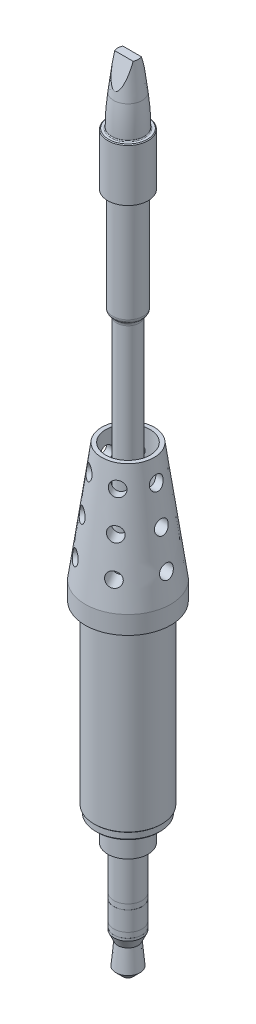
SolidWorks part; units mm, degrees
other "Body"
other "Jack Base"
other "Jack Divider 1"
other "Jack Middle"
other "Jack Divider 2"
other "Jack Tip"
other "Guard"
ref_plane "Front Plane" through (0, 0, 0) normal (0, 0, 1) x (1, 0, 0)
ref_plane "Top Plane" through (0, 0, 0) normal (0, 1, 0) x (1, 0, 0)
ref_plane "Right Plane" through (0, 0, 0) normal (1, 0, 0) x (0, 0, -1)
sketch "Sketch1" plane through (0, 0, 0) normal (0, 1, 0) x (1, 0, 0)
  circle A0 centre (0, 0) radius 4.2
  dimension "D1" = 8.4
extrude "Boss-Extrude1" add sketch "Sketch1" along normal blind 22
sketch "Sketch9" plane through (0, 22, 0) normal (0, 1, 0) x (1, 0, 0)
  circle A0 centre (0, 0) radius 3.4
  dimension "D1" = 6.8
extrude "Boss-Extrude8" add sketch "Sketch9" along normal blind 0.7
sketch "Sketch10" plane through (0, 22.7, 0) normal (0, 1, 0) x (1, 0, 0)
  circle A0 centre (0, 0) radius 3.75
  dimension "D1" = 7.5
extrude "Boss-Extrude9" add sketch "Sketch10" along normal blind 2.8
sketch "Sketch11" plane through (0, 25.5, 0) normal (0, 1, 0) x (1, 0, 0)
  circle A0 centre (0, 0) radius 1.8
  dimension "D1" = 3.6
extrude "Boss-Extrude10" add sketch "Sketch11" along normal blind 2.9
sketch "Sketch12" plane through (0, 28.4, 0) normal (0, 1, 0) x (1, 0, 0)
  circle A0 centre (0, 0) radius 1.4
  dimension "D1" = 2.8
extrude "Boss-Extrude11" add sketch "Sketch12" along normal blind 24.25
sketch "Sketch13" plane through (0, 52.65, 0) normal (0, 1, 0) x (1, 0, 0)
  circle A0 centre (0, 0) radius 1.9
  dimension "D1" = 3.8
extrude "Boss-Extrude12" add sketch "Sketch13" along normal blind 13.2
sketch "Sketch14" plane through (0, 65.85, 0) normal (0, 1, 0) x (1, 0, 0)
  circle A0 centre (0, 0) radius 2.5
  dimension "D1" = 5
extrude "Boss-Extrude13" add sketch "Sketch14" along normal blind 6.9
sketch "Sketch15" plane through (0, 0, 0) normal (1, 0, 0) x (0, 0, -1)
  line L0 (0, -927.2764) -> (0, 49072.7236) construction
  line L2 (-2, 72.75) -> (-2, 74.75)
  line L3 (2.5, 72.75) -> (-2.5, 72.75) construction
  line L4 (-2, 74.75) -> (-1.25, 80.75)
  line L5 (-1.25, 80.75) -> (0, 80.75)
  line L6 (0, 80.75) -> (0, 72.75)
  line L7 (0, 72.75) -> (-2, 72.75)
  dimension "D1" = 4
  dimension "D2" = 2.5
  dimension "D3" = 8
  dimension "D4" = 2
revolve "Revolve2" add sketch "Sketch15" angle 360 about L0
sketch "Sketch16" plane through (0, 0, 0) normal (1, 0, 0) x (0, 0, -1)
  line L0 (1.25, 80.75) -> (-1.25, 80.75) construction
  line L1 (2, 74.75) -> (-2, 74.75) construction
  line L3 (1.25, 80.75) -> (-1.25, 80.75) construction
  line L4 (-1.25, 80.75) -> (-2.1233, 74.75) construction
  line L5 (1.25, 80.75) -> (2, 74.75) construction
  line L6 (-0.5, 80.75) -> (0.5, 80.75)
  line L7 (0.5, 80.75) -> (1.65, 77.5504)
  line L8 (1.65, 77.5504) -> (1.25, 80.75)
  line L9 (1.25, 80.75) -> (0.5, 80.75)
  line L10 (0, 4.62) -> (0, -4.62) construction
  line L11 (-1.65, 77.5504) -> (-1.25, 80.75)
  line L12 (-0.5, 80.75) -> (-1.65, 77.5504)
  line L13 (-1.25, 80.75) -> (-0.5, 80.75)
  point P7 (0, 80.75)
  dimension "D2" = 1
  dimension "D3" = 3.4
extrude "Cut-Extrude1" cut sketch "Sketch16" against normal through all both and the other way through all contours L13 L11 L12 | L8 L9 L7 region at (0, 79.6835, -1.1333) region at (0, 79.6835, 1.1333)
fillet "Fillet1" radius 30 1 edges at (0, 74.75, -2)
chamfer "Chamfer1" distance 0.1 angle 45 2 edges at (0, 0, 4.2) (0, 72.75, 2.5)
chamfer "Chamfer2" distance 0.4 angle 45 2 edges at (0, 25.5, 3.75) (0, 22.7, 3.75)
chamfer "Chamfer3" distance 0.6 angle 30 1 edges at (0, 65.85, 2.5) first distance on face at (0, 65.85, 1.9)
fillet "Fillet3" radius 0.1 1 edges at (0, 72.75, -2)
chamfer "Chamfer4" distance 0.6 angle 45 1 edges at (0, 52.65, 1.9)
fillet "Fillet4" radius 0.6 2 edges at (0, 52.75, 1.4) (0, 53.25, 1.9)
sketch "Sketch2" plane through (0, 0, 0) normal (0, -1, 0) x (1, 0, 0)
  circle A0 centre (0, 0) radius 4
  dimension "D1" = 8
extrude "Boss-Extrude2" add sketch "Sketch2" along normal blind 1 separate body
sketch "Sketch3" plane through (0, -1, 0) normal (0, -1, 0) x (1, 0, 0)
  circle A0 centre (0, 0) radius 2.5
  dimension "D1" = 5
extrude "Boss-Extrude3" add sketch "Sketch3" along normal blind 3
sketch "Sketch4" plane through (0, -4, 0) normal (0, -1, 0) x (1, 0, 0)
  circle A0 centre (0, 0) radius 1.75
  dimension "D1" = 3.5
extrude "Boss-Extrude4" add sketch "Sketch4" along normal blind 5.35
sketch "Sketch5" plane through (0, -9.35, 0) normal (0, -1, 0) x (1, 0, 0)
  circle A2 centre (0, 0) radius 1.74
  circle A3 centre (0, 0) radius 1.74
  dimension "D1" = 0.01
extrude "Boss-Extrude5" add sketch "Sketch5" along normal blind 0.65 separate body
sketch "Sketch6" plane through (0, -10, 0) normal (0, -1, 0) x (1, 0, 0)
  circle A0 centre (0, 0) radius 1.75 construction
  circle A1 centre (0, 0) radius 1.75
extrude "Boss-Extrude6" add sketch "Sketch6" along normal blind 2.4 separate body
sketch "Sketch7" plane through (0, -12.4, 0) normal (0, -1, 0) x (1, 0, 0)
  circle A2 centre (0, 0) radius 1.74
  circle A3 centre (0, 0) radius 1.74
  dimension "D1" = 0.01
extrude "Boss-Extrude7" add sketch "Sketch7" along normal blind 0.65 separate body
sketch "Sketch8" plane through (0, 0, 0) normal (1, 0, 0) x (0, 0, -1)
  line L0 (0, -1013.0181) -> (0, 48986.9819) construction
  line L2 (0, -13.05) -> (-1.75, -13.05)
  line L3 (-1.74, -13.05) -> (1.74, -13.05) construction
  line L4 (-1.75, -13.05) -> (-1.75, -13.35)
  line L5 (-1.75, -13.35) -> (-1.25, -14.4362)
  line L6 (-1.25, -14.4362) -> (-1.5, -17.225)
  line L7 (-1.5, -17.225) -> (-0.625, -18.1)
  line L8 (-0.625, -18.1) -> (0, -18.1)
  line L9 (0, -18.1) -> (0, -13.05)
  line L10 (-4, -1) -> (4, -1) construction
  point P12 (-0.3125, -18.1)
  dimension "D1" = 3.5
  dimension "D2" = 3
  dimension "D3" = 1.25
  dimension "D4" = 17.1
  dimension "D5" = 2.5
  dimension "D6" = 0.3
  dimension "D7" = 2.8
  dimension "D8" = 45
revolve "Revolve1" add sketch "Sketch8" angle 360 about L0
chamfer "Chamfer5" distance 0.2 angle 45 1 edges at (0, -1, -4)
sketch "Sketch17" plane through (0, 22, 0) normal (0, 1, 0) x (1, 0, 0)
  circle A0 centre (0, 0) radius 5.3
  dimension "D1" = 10.6
extrude "Boss-Extrude14" add sketch "Sketch17" along normal blind 2.25 separate body
sketch "Sketch18" plane through (0, 0, 0) normal (1, 0, 0) x (0, 0, -1)
  line L0 (-5.3, 24.25) -> (-3.25, 39)
  line L1 (-3.25, 39) -> (0, 39)
  line L2 (0, 5.83) -> (0, -5.83) construction
  line L3 (0, 39) -> (0, 24.25)
  line L4 (5.3, 24.25) -> (-5.3, 24.25) construction
  line L5 (0, 24.25) -> (-5.3, 24.25)
  line L6 (4.2, 22) -> (-4.2, 22) construction
  line L7 (0, -958.0782) -> (0, 49041.9218) construction
  dimension "D1" = 17
  dimension "D2" = 6.5
revolve "Revolve3" add sketch "Sketch18" angle 360 about L7
sketch "Sketch19" plane through (0, 39, 0) normal (0, 1, 0) x (1, 0, 0)
  circle A2 centre (0, 0) radius 2.75
  circle A3 centre (0, 0) radius 2.75
  dimension "D1" = 0.5
extrude "Cut-Extrude2" cut sketch "Sketch19" against normal through all
sketch "Sketch20" plane through (0, 22, 0) normal (0, -1, 0) x (1, 0, 0)
  circle A0 centre (0, 0) radius 3.8
  dimension "D1" = 7.6
extrude "Cut-Extrude4" cut sketch "Sketch20" against normal blind 3.8
fillet "Chamfer6" radius 0.4 1 edges at (0, 22, -3.8) type face fillet profile chamfer first side face at (0, 25.8, -3.8) second side face at (0, 22, -3.8)
sketch "Sketch21" plane through (0, 0, 0) normal (1, 0, 0) x (0, 0, -1)
  line L0 (0, 39) -> (0, 24.25) construction
  line L1 (3.25, 39) -> (-3.25, 39) construction
  line L2 (0, 5.83) -> (0, -5.83) construction
  line L3 (-5.3, 24.25) -> (5.3, 24.25) construction
  line L4 (0, 36.45) -> (0, 32) construction
  circle A0 centre (0, 36.45) radius 0.85
  circle A1 centre (0, 32) radius 0.85
  circle A2 centre (0, 27.55) radius 0.85
  dimension "D1" = 1.7
  dimension "D2" = 2.55
  dimension "D4" = 4.45
  dimension "D3" = 3
extrude "Cut-Extrude6" cut sketch "Sketch21" against normal through all both and the other way through all
pattern_circular "CirPattern1" count 3 over 360 about axis through (0, 39, 0) along (0, 1, 0) of "Cut-Extrude6" reverse direction yes
ref_axis "Axis1" through (0, 22, 0) along (0, -1, 0)
